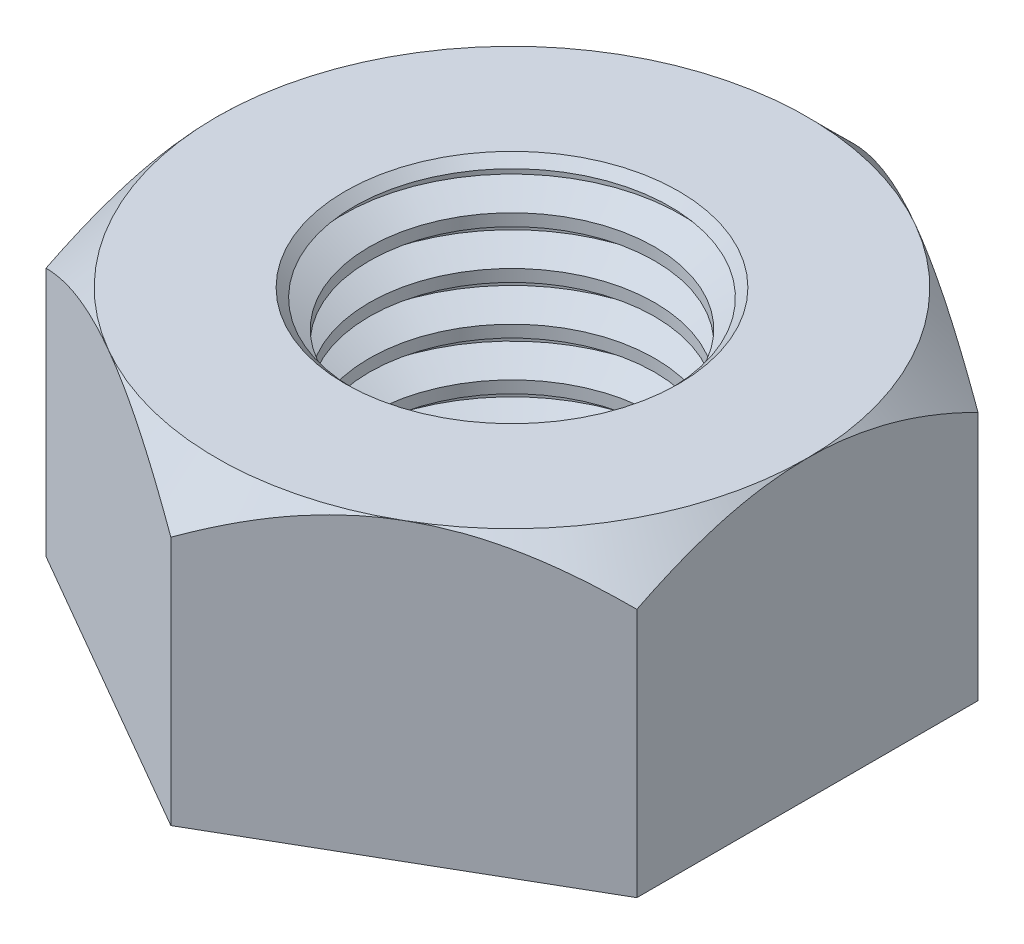
SolidWorks part; units mm, degrees
ref_plane "Front" through (0, 0, 0) normal (0, 0, 1) x (1, 0, 0)
ref_plane "Top" through (0, 0, 0) normal (0, 1, 0) x (1, 0, 0)
ref_plane "Right" through (0, 0, 0) normal (1, 0, 0) x (0, 0, -1)
sketch "Sketch1" plane through (0, 0, 0) normal (0, 1, 0) x (1, 0, 0)
  line L1 (0, 6.4158) -> (-5.5563, 3.2079)
  line L2 (-5.5563, 3.2079) -> (-5.5563, -3.2079)
  line L3 (-5.5563, -3.2079) -> (0, -6.4158)
  line L4 (0, -6.4158) -> (5.5562, -3.2079)
  line L5 (5.5562, -3.2079) -> (5.5562, 3.2079)
  line L6 (5.5562, 3.2079) -> (0, 6.4158)
  circle A0 centre (0, 0) radius 5.5563 construction
  dimension "Hex Flats" = 11.1125
extrude "Extrude1" add sketch "Sketch1" along normal blind 5.5562
sketch "Sketch3" plane through (0, 0, 0) normal (1, 0, 0) x (0, 0, -1)
  line L0 (5.5562, 5.5562) -> (6.4158, 4.6967)
  line L1 (3.2079, 5.5562) -> (6.4158, 5.5562) construction
  line L2 (6.4158, 5.5562) -> (6.4158, 0) construction
  line L3 (6.4158, 4.6967) -> (6.4158, 5.5562)
  line L4 (6.4158, 5.5562) -> (5.5562, 5.5562)
  line L5 (0, 0.542) -> (0, -0.542) construction
  dimension "D1" = 45
  dimension "D2" = 11.1125
revolve "Cut-Revolve2" cut sketch "Sketch3" angle 360 about L5
sketch "Sketch2" plane through (0, 0, 0) normal (0, 0, 1) x (1, 0, 0)
  line L0 (0, 1.6636) -> (0, -0.3796) construction
  line L1 (0, 5.5562) -> (2.684, 5.5562)
  line L3 (0, 5.5562) -> (5.5562, 5.5562) construction
  line L4 (0, 4.6491) -> (2.684, 4.6491)
  line L5 (2.684, 5.5562) -> (3.175, 5.2728)
  line L6 (3.175, 5.2728) -> (3.175, 5.1594)
  line L7 (3.175, 5.1594) -> (2.684, 4.8759)
  line L9 (2.684, 4.6491) -> (2.684, 4.8759)
  line L10 (0, 4.6491) -> (0, 5.5562)
  line L11 (2.684, 5.5562) -> (2.684, 4.8759) construction
  line L12 (3.175, 5.2161) -> (2.684, 5.2161) construction
  dimension "D1" = 60
  dimension "D2" = 0.2268
  dimension "D5" = 0.1134
  dimension "Pitch" = 0.9071
  dimension "Major Dia." = 6.35
revolve "Cut-Revolve1" cut sketch "Sketch2" angle 360 about L0
pattern_linear "LPattern2" count 7 spacing 0.9071 along (0, -1, 0) of "Cut-Revolve1"
chamfer "Chamfer1" distance 0.4536 angle 45 1 edges at (0, 5.5562, 2.684) first distance on face at (0, 5.5562, 0)
equation "\"D5@Sketch2\"=\"Pitch@Sketch2\"/8"
equation "\"D2@Sketch2\"=\"Pitch@Sketch2\"/4"
equation "\"D3@LPattern2\"=\"Pitch@Sketch2\""
equation "\"D1@LPattern2\"=int(\"Height@Extrude1\"/\"Pitch@Sketch2\")+1"
equation "\"D2@Sketch3\"=\"Hex Flats@Sketch1\""
equation "\"D1@Chamfer1\"=\"Pitch@Sketch2\"/2"
